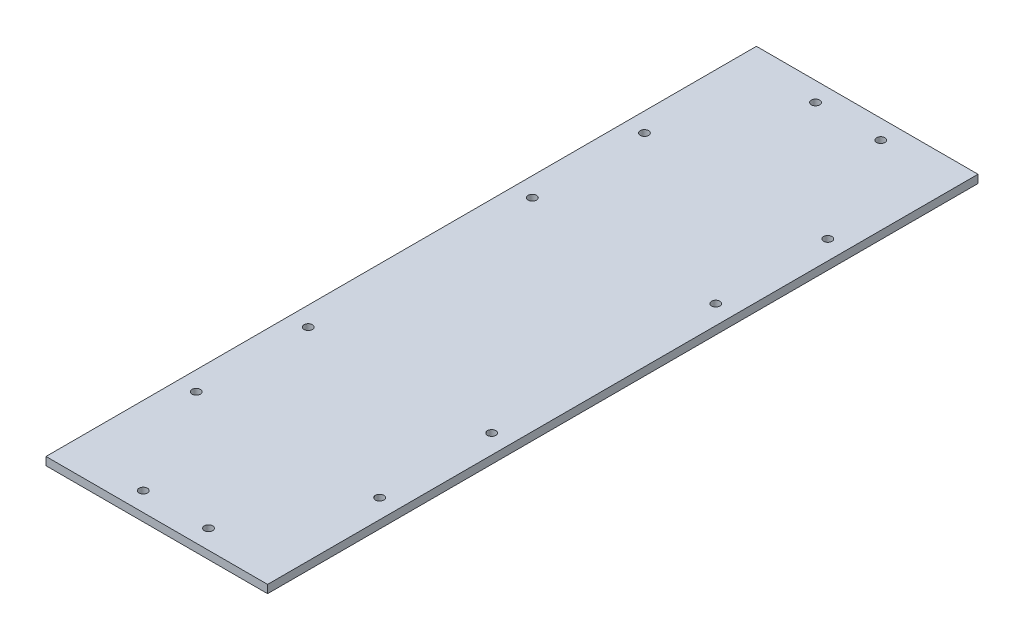
SolidWorks part; units mm, degrees
ref_plane "Front Plane" through (0, 0, 0) normal (0, 0, 1) x (1, 0, 0)
ref_plane "Top Plane" through (0, 0, 0) normal (0, 1, 0) x (1, 0, 0)
ref_plane "Right Plane" through (0, 0, 0) normal (1, 0, 0) x (0, 0, -1)
sketch "Sketch1" plane through (0, 0, 0) normal (0, 1, 0) x (1, 0, 0)
  line L0 (0, 139.7) -> (0, -139.7) construction
  line L1 (-43.575, 139.7) -> (43.575, 139.7)
  line L2 (-43.575, 139.7) -> (-43.575, -139.7)
  line L3 (-43.575, -139.7) -> (43.575, -139.7)
  line L4 (43.575, 139.7) -> (43.575, -139.7)
  line L5 (-43.575, 139.7) -> (43.575, -139.7) construction
  line L6 (-43.575, -139.7) -> (43.575, 139.7) construction
  line L7 (-36.075, 132.2) -> (36.075, 132.2) construction
  line L8 (-36.075, 132.2) -> (-36.075, -132.2) construction
  line L9 (-36.075, -132.2) -> (36.075, -132.2) construction
  line L10 (36.075, 132.2) -> (36.075, -132.2) construction
  line L11 (-36.075, 132.2) -> (36.075, -132.2) construction
  line L12 (-36.075, -132.2) -> (36.075, 132.2) construction
  line L13 (-43.575, 0) -> (43.575, 0) construction
  line L14 (-36.075, -132.2) -> (36.075, -132.2) construction
  circle A0 centre (-12.835, 132.2) radius 1.65
  circle A1 centre (-36.075, 88.1333) radius 1.65
  circle A2 centre (-36.075, 44.0667) radius 1.65
  circle A3 centre (36.075, 44.0667) radius 1.65
  circle A4 centre (36.075, 88.1333) radius 1.65
  circle A5 centre (12.835, 132.2) radius 1.65
  circle A6 centre (12.835, -132.2) radius 1.65
  circle A7 centre (36.075, -88.1333) radius 1.65
  circle A8 centre (36.075, -44.0667) radius 1.65
  circle A9 centre (-36.075, -44.0667) radius 1.65
  circle A10 centre (-36.075, -88.1333) radius 1.65
  circle A11 centre (-12.835, -132.2) radius 1.65
  point P0 (0, 0)
  point P6 (0, 0)
  dimension "D5" = 3.3
  dimension "D6" = 3.3
  dimension "D7" = 3.3
  dimension "D1" = 7.5
  dimension "D2" = 7.5
  dimension "D3" = 279.4
  dimension "D4" = 87.15
  dimension "D8" = 23.24
  dimension "D9" = 44.0667
  dimension "D10" = 44.0667
  dimension "D11" = 44.0667
extrude "Boss-Extrude1" add sketch "Sketch1" along normal blind 3.175
equation "\"D6@Sketch1\"=\"D5@Sketch1\""
equation "\"D7@Sketch1\"=\"D5@Sketch1\""
equation "\"D10@Sketch1\"=\"D9@Sketch1\""
